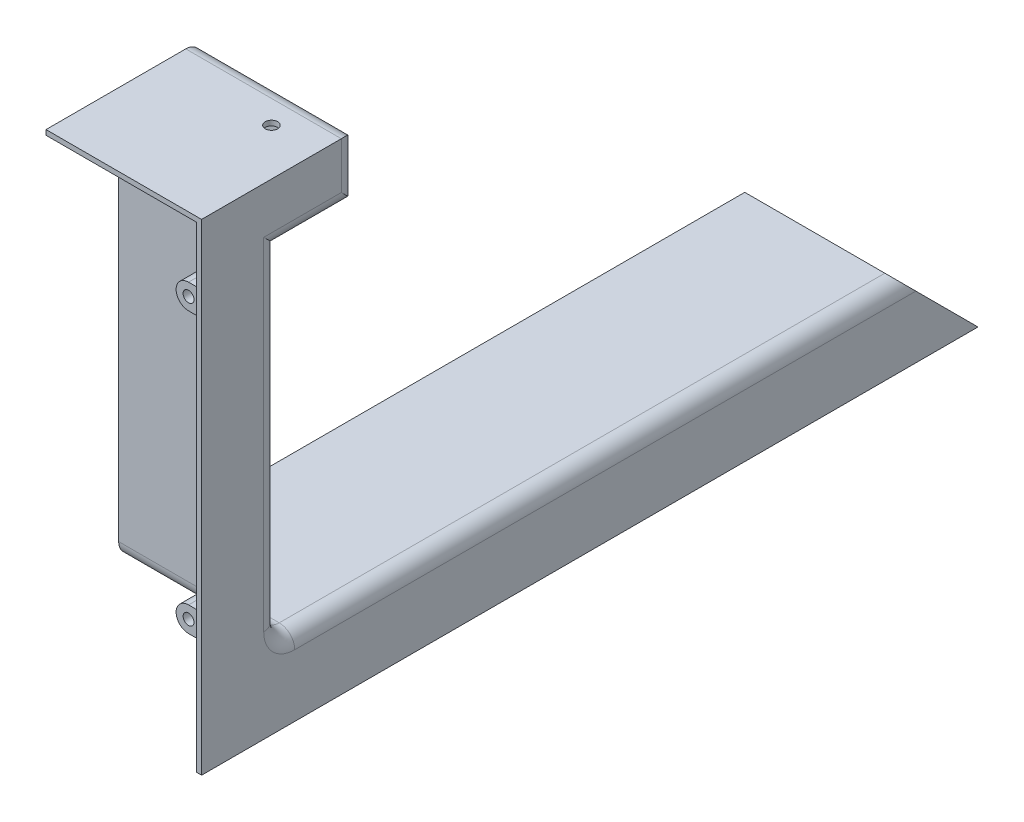
SolidWorks part; units mm, degrees
ref_plane "Front Plane" through (0, 0, 0) normal (0, 0, 1) x (1, 0, 0)
ref_plane "Top Plane" through (0, 0, 0) normal (0, 1, 0) x (1, 0, 0)
ref_plane "Right Plane" through (0, 0, 0) normal (1, 0, 0) x (0, 0, -1)
sketch "Sketch1" plane through (0, 0, 0) normal (1, 0, 0) x (0, 0, -1)
  line L0 (0, 155) -> (0, 0)
  line L1 (0, 0) -> (250, 0)
  line L2 (250, 0) -> (225, 25)
  line L3 (225, 25) -> (25, 25)
  line L4 (25, 25) -> (25, 135)
  line L5 (25, 155) -> (0, 155)
  line L6 (25, 155) -> (50, 155)
  line L7 (50, 155) -> (50, 135)
  line L8 (50, 135) -> (25, 135)
  dimension "D1" = 155
  dimension "D2" = 250
  dimension "D3" = 25
  dimension "D4" = 25
  dimension "D5" = 45
  dimension "D6" = 25
  dimension "D7" = 20
  dimension "D8" = 25
extrude "Boss-Extrude1" add sketch "Sketch1" along normal blind 1.6
sketch "Sketch2" plane through (0, 0, 0) normal (1, 0, 0) x (0, 0, -1)
  line L0 (225, 25) -> (25, 25) construction
  line L1 (25, 25) -> (25, 135) construction
  line L2 (25, 135) -> (50, 135) construction
  line L3 (50, 135) -> (50, 155) construction
  line L4 (50, 155) -> (0, 155) construction
  line L5 (225, 25) -> (25, 25)
  line L6 (25, 25) -> (25, 135)
  line L7 (25, 135) -> (50, 135)
  line L8 (50, 135) -> (50, 155)
  line L9 (50, 155) -> (0, 155)
  line L10 (225, 25) -> (225, 1.6)
  line L11 (223.4, 0) -> (250, 0)
  line L12 (48.4, 153.4) -> (0, 153.4)
  line L13 (48.4, 136.6) -> (48.4, 153.4)
  line L14 (23.4, 136.6) -> (48.4, 136.6)
  line L15 (23.4, 23.4) -> (23.4, 136.6)
  line L16 (223.4, 23.4) -> (23.4, 23.4)
  line L17 (223.4, 23.4) -> (223.4, 0)
  line L18 (0, 155) -> (0, 153.4)
  line L21 (225, 1.6) -> (248.4, 1.6)
  line L22 (250, 0) -> (225, 25) construction
  line L23 (248.4, 1.6) -> (250, 0)
  line L25 (225, 25) -> (225, 0) construction
  dimension "D2" = 1.6
  dimension "D1" = 1.6
extrude "Boss-Extrude2" add sketch "Sketch2" against normal blind 48.5
fillet "Fillet1" radius 5 12 edges at (1.6, 80, -25) (0, 80, -23.4) (1.6, 145, -50) (1.6, 135, -37.5) (0, 145, -48.4) (0, 136.6, -35.9) (-23.45, 155, -50) (-24.25, 153.4, -48.4) (-24.25, 23.4, -23.4) (-23.45, 25, -25) (1.6, 25, -125) (0, 23.4, -123.4)
fillet "Fillet2" radius 5 2 edges at (0, 12.633, -225) (0, 1.6, -236.7)
ref_plane "Plane1" through (0, 6, 0) normal (0, -1, 0) x (-1, 0, 0)
sketch "Sketch3" plane through (0, 6, 0) normal (0, -1, 0) x (1, 0, 0)
  line L0 (-48.5, -223.4) -> (-48.5, -144.7093) construction
  line L1 (0, -34.5) -> (-1.6381, -34.5)
  line L2 (-1.6381, -32.0028) -> (0, -31.5)
  line L3 (-1.6381, -211.5) -> (0, -211.5)
  line L4 (0, -214.5) -> (-1.6381, -214.9988)
  line L5 (0, -31.5) -> (0, -34.5)
  line L6 (0, -211.5) -> (0, -214.5)
  line L13 (-98.6, 0) -> (-98.6, -250)
  line L14 (-98.6, -250) -> (-48.5, -250)
  line L15 (-48.5, -250) -> (-48.5, -223.4)
  line L16 (-48.5, -223.4) -> (-97, -223.4)
  line L17 (-97, -223.4) -> (-97, 0)
  line L18 (-90, -33.4) -> (-7.114, -33.4) construction
  line L19 (-7.114, -213.4) -> (-90, -213.4) construction
  line L20 (0, -28.4) -> (0, -223.4) construction
  line L24 (-97, 0) -> (-98.6, 0)
  line L25 (-98.6, 0) -> (-98.6, -250) construction
  line L26 (-98.6, -250) -> (-48.5, -250) construction
  line L27 (-48.5, -250) -> (-48.5, -223.4) construction
  line L28 (-48.5, -223.4) -> (-97, -223.4) construction
  line L29 (-97, -223.4) -> (-97, 0) construction
  line L36 (-97, 0) -> (-98.6, 0) construction
  arc A0 (-3.9375, -35.5731) -> (-1.6381, -34.5) centre (-1.6381, -37.5) cw
  arc A1 (-3.9375, -35.5731) -> (-4.3217, -30.7513) centre (-7.114, -33.4) cw
  arc A2 (-1.6381, -32.0028) -> (-4.3217, -30.7513) centre (-1.6381, -28.5) cw
  arc A3 (-1.6381, -211.5) -> (-3.9361, -210.4286) centre (-1.6381, -208.5) cw
  arc A4 (-3.5218, -215.8545) -> (-3.9361, -210.4286) centre (-7.114, -213.4) cw
  arc A5 (-3.5218, -215.8545) -> (-1.6381, -214.9988) centre (-1.6381, -217.5) cw
  circle A18 centre (-7.114, -213.4) radius 1.5
  circle A19 centre (-90, -213.4) radius 1.5 construction
  circle A20 centre (-7.114, -33.4) radius 1.5
  circle A21 centre (-90, -33.4) radius 1.5 construction
  dimension "D1" = 0
extrude "Boss-Extrude3" add sketch "Sketch3" against normal up to next contours L2 A2 A1 A0 L1 A20 | A4 A5 L4 L3 A3 A18 region at (-0.819, 6, -34.366) region at (-0.819, 6, -211.6439)
ref_plane "Plane2" through (0, 0, -3.9) normal (0, 0, 1) x (1, 0, 0)
sketch "Sketch4" plane through (0, 0, -3.9) normal (0, 0, 1) x (1, 0, 0)
  line L1 (-6.5, 131.5) -> (0, 131.5)
  line L3 (-6.5, 123.5) -> (0, 123.5)
  line L4 (0, 131.5) -> (0, 123.5)
  line L5 (-6.5, 41.5) -> (0, 41.5)
  line L7 (-6.5, 33.5) -> (0, 33.5)
  line L8 (0, 41.5) -> (0, 33.5)
  circle A0 centre (-6.5, 127.5) radius 1.75 construction
  circle A1 centre (-6.5, 37.5) radius 1.75 construction
  circle A2 centre (-6.5, 127.5) radius 1.75
  circle A3 centre (-6.5, 37.5) radius 1.75
  arc A4 (-6.5, 131.5) -> (-6.5, 123.5) centre (-6.5, 127.5) ccw
  arc A5 (-6.5, 41.5) -> (-6.5, 33.5) centre (-6.5, 37.5) ccw
  dimension "D1" = 8
extrude "Boss-Extrude4" add sketch "Sketch4" against normal up to surface (19.5 mm away) up to face at (-26.75, 82.5, -23.4)
sketch "Croquis1" plane through (0, 135, 0) normal (0, -1, 0) x (1, 0, 0)
  line L0 (-13.4, -37.5) -> (-63.4, -37.5) construction
  line L1 (-13.4, -45.5) -> (-63.4, -45.5)
  line L2 (-13.4, -29.5) -> (-63.4, -29.5)
  line L3 (-3.4, -50) -> (-3.4, -25) construction
  arc A0 (-13.4, -45.5) -> (-13.4, -29.5) centre (-13.4, -37.5) ccw
  arc A1 (-63.4, -29.5) -> (-63.4, -45.5) centre (-63.4, -37.5) ccw
  point P2 (-38.4, -37.5)
  point P9 (-3.4, -37.5)
  dimension "D1" = 8
  dimension "D2" = 10
  dimension "D3" = 50
extrude "Cortar-Extruir1" cut sketch "Croquis1" against normal up to next
sketch "Croquis2" plane through (0, 153.4, 0) normal (0, -1, 0) x (1, 0, 0)
  arc A0 (-13.4, -45.5) -> (-13.4, -29.5) centre (-13.4, -37.5) ccw construction
  arc A1 (-13.4, -45.5) -> (-13.4, -29.5) centre (-13.4, -37.5) ccw construction
  circle A2 centre (-13.4, -37.5) radius 2
  dimension "D1" = 4
extrude "Cortar-Extruir2" cut sketch "Croquis2" against normal up to next
equation "\"D2@Sketch2\"=\"D1@Sketch2\""
